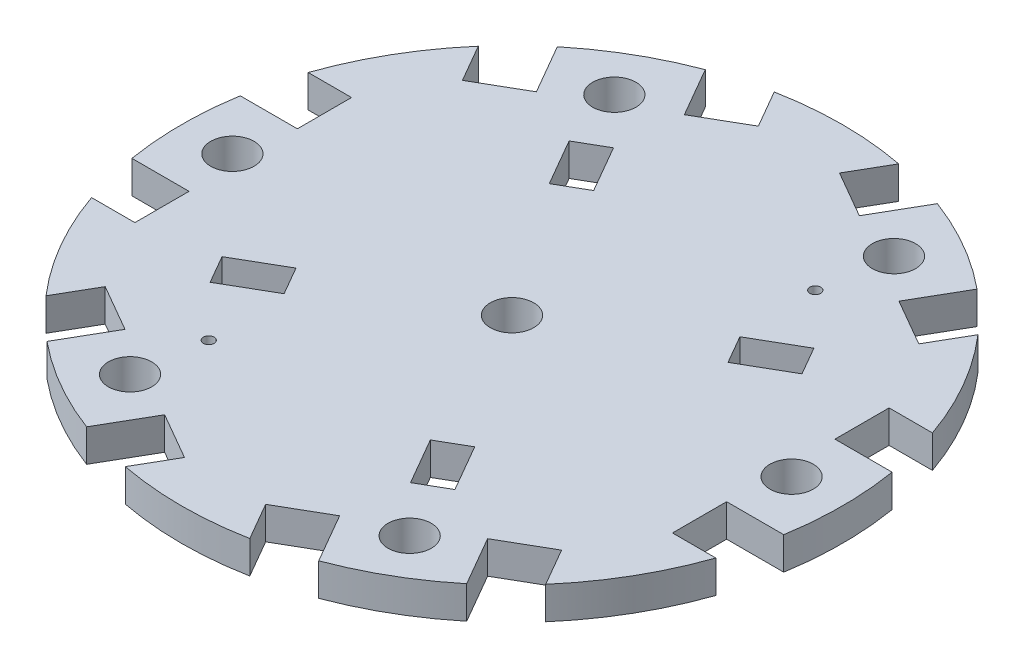
SolidWorks part; units mm, degrees
ref_plane "Alzado" through (0, 0, 0) normal (0, 0, 1) x (1, 0, 0)
ref_plane "Planta" through (0, 0, 0) normal (0, 1, 0) x (1, 0, 0)
ref_plane "Vista lateral" through (0, 0, 0) normal (1, 0, 0) x (0, 0, -1)
sketch "Croquis1" plane through (0, 0, 0) normal (0, 1, 0) x (1, 0, 0)
  circle A0 centre (0, 0) radius 30.5
extrude "Saliente-Extruir1" add sketch "Croquis1" along normal blind 3
sketch "Croquis2" plane through (0, 3, 0) normal (0, 1, 0) x (1, 0, 0)
  circle A0 centre (0, 0) radius 2
extrude "Cortar-Extruir1" cut sketch "Croquis2" against normal blind 4
sketch "Croquis5" plane through (0, 3, 0) normal (0, 1, 0) x (1, 0, 0)
  line L1 (28.8141, -5) -> (30.0874, -5)
  line L2 (28.8141, 5) -> (30.0874, 5)
  line L3 (-24.8141, 10) -> (-28.8141, 10)
  line L4 (24.8141, -5) -> (24.8141, -10)
  line L5 (-24.8141, -10) -> (-28.8141, -10)
  line L6 (24.8141, -5) -> (28.8141, -5)
  line L7 (24.8141, 5) -> (24.8141, 10)
  line L8 (-24.8141, 5) -> (-28.8141, 5)
  line L9 (-24.8141, 5) -> (-24.8141, 10)
  line L10 (-24.8141, -5) -> (-28.8141, -5)
  line L11 (-24.8141, -5) -> (-24.8141, -10)
  line L12 (24.8141, 5) -> (28.8141, 5)
  line L13 (24.8141, -10) -> (28.8141, -10)
  line L14 (24.8141, 10) -> (28.8141, 10)
  line L15 (-28.8141, 5) -> (-30.0874, 5)
  line L16 (-28.8141, -5) -> (-30.0874, -5)
  line L17 (18.7372, 22.4537) -> (19.3738, 23.5564)
  line L18 (-24.8141, 0) -> (-12.407, -21.4896)
  line L19 (-12.407, -21.4896) -> (12.407, -21.4896)
  line L20 (12.407, -21.4896) -> (24.8141, 0)
  line L21 (24.8141, 0) -> (12.407, 21.4896)
  line L22 (12.407, 21.4896) -> (-12.407, 21.4896)
  line L23 (-12.407, 21.4896) -> (-24.8141, 0)
  line L24 (-21.0673, -16.4896) -> (-23.0673, -19.9537)
  line L25 (-3.7468, -26.4896) -> (-5.7468, -29.9537)
  line L26 (-16.7372, -18.9896) -> (-18.7372, -22.4537)
  line L27 (-16.7372, -18.9896) -> (-21.0673, -16.4896)
  line L28 (-8.0769, -23.9896) -> (-10.0769, -27.4537)
  line L29 (-8.0769, -23.9896) -> (-3.7468, -26.4896)
  line L30 (-18.7372, -22.4537) -> (-19.3738, -23.5564)
  line L31 (-10.0769, -27.4537) -> (-10.7136, -28.5564)
  line L32 (10.0769, 27.4537) -> (10.7136, 28.5564)
  line L33 (16.7372, 18.9896) -> (21.0673, 16.4896)
  line L34 (16.7372, 18.9896) -> (18.7372, 22.4537)
  line L35 (8.0769, 23.9896) -> (3.7468, 26.4896)
  line L36 (8.0769, 23.9896) -> (10.0769, 27.4537)
  line L37 (21.0673, 16.4896) -> (23.0673, 19.9537)
  line L38 (3.7468, 26.4896) -> (5.7468, 29.9537)
  line L39 (-3.7468, 26.4896) -> (-5.7468, 29.9537)
  line L40 (-21.0673, 16.4896) -> (-23.0673, 19.9537)
  line L41 (-8.0769, 23.9896) -> (-10.0769, 27.4537)
  line L42 (-8.0769, 23.9896) -> (-3.7468, 26.4896)
  line L43 (-16.7372, 18.9896) -> (-18.7372, 22.4537)
  line L44 (-16.7372, 18.9896) -> (-21.0673, 16.4896)
  line L45 (-10.0769, 27.4537) -> (-10.7136, 28.5564)
  line L46 (-18.7372, 22.4537) -> (-19.3738, 23.5564)
  line L47 (10.0769, -27.4537) -> (10.7136, -28.5564)
  line L48 (18.7372, -22.4537) -> (19.3738, -23.5564)
  line L49 (8.0769, -23.9896) -> (3.7468, -26.4896)
  line L50 (8.0769, -23.9896) -> (10.0769, -27.4537)
  line L51 (16.7372, -18.9896) -> (21.0673, -16.4896)
  line L52 (16.7372, -18.9896) -> (18.7372, -22.4537)
  line L53 (3.7468, -26.4896) -> (5.7468, -29.9537)
  line L54 (21.0673, -16.4896) -> (23.0673, -19.9537)
  circle A0 centre (0, 0) radius 21.4896 construction
  circle A1 centre (0, 0) radius 30.5 construction
  arc A2 (-28.8141, 10) -> (-30.0874, 5) centre (0, 0) ccw
  arc A3 (-5.7468, 29.9537) -> (-10.7136, 28.5564) centre (0, 0) ccw
  arc A4 (-30.0874, -5) -> (-28.8141, -10) centre (0, 0) ccw
  arc A5 (30.0874, -5) -> (28.8141, -10) centre (0, 0) cw
  arc A6 (28.8141, 10) -> (30.0874, 5) centre (0, 0) cw
  arc A7 (-23.0673, -19.9537) -> (-19.3738, -23.5564) centre (0, 0) ccw
  arc A8 (-10.7136, -28.5564) -> (-5.7468, -29.9537) centre (0, 0) ccw
  arc A9 (-19.3738, 23.5564) -> (-23.0673, 19.9537) centre (0, 0) ccw
  arc A10 (19.3738, 23.5564) -> (23.0673, 19.9537) centre (0, 0) cw
  arc A11 (5.7468, 29.9537) -> (10.7136, 28.5564) centre (0, 0) cw
  arc A12 (10.7136, -28.5564) -> (5.7468, -29.9537) centre (0, 0) cw
  arc A13 (23.0673, -19.9537) -> (19.3738, -23.5564) centre (0, 0) cw
  circle M2 centre (0, 0) radius 30.5
extrude "Cortar-Extruir3" cut sketch "Croquis5" against normal blind 4 contours L15 L8 L9 L3 M2 | L14 L7 L12 L2 M2 | L4 L13 L1 L6 M2 | L54 L51 L52 L48 M2 | L49 L53 L47 L50 M2 | L28 L31 L25 L29 M2 | L30 L26 L27 L24 M2 | L10 L16 L5 L11 M2 | L43 L46 L40 L44 M2 | L45 L41 L42 L39 M2 | L38 L35 L36 L32 M2 | L33 L37 L17 L34 M2 region at (27.1844, 3, 7.3876) region at (19.99, 3, 19.8486) region at (27.1844, 3, -7.3876) region at (7.1944, 3, 27.2362) region at (19.99, 3, -19.8486) region at (-7.1944, 3, 27.2362) region at (7.1944, 3, -27.2362) region at (-19.99, 3, 19.8486) region at (-7.1944, 3, -27.2362) region at (-27.1844, 3, 7.3876) region at (-19.99, 3, -19.8486) region at (-27.1844, 3, -7.3876)
sketch "Croquis7" plane through (0, 3, 0) normal (0, 1, 0) x (1, 0, 0)
  line L2 (25.8141, 0) -> (12.907, 22.3556)
  line L3 (12.907, 22.3556) -> (-12.907, 22.3556)
  line L4 (-12.907, 22.3556) -> (-25.8141, 0)
  line L5 (-25.8141, 0) -> (-12.907, -22.3556)
  line L6 (-12.907, -22.3556) -> (12.907, -22.3556)
  line L7 (12.907, -22.3556) -> (25.8141, 0)
  circle A0 centre (25.8141, 0) radius 2
  circle A4 centre (-25.8141, 0) radius 2
  circle A5 centre (0, 0) radius 22.3556 construction
  circle A6 centre (12.907, 22.3556) radius 2
  circle A7 centre (-12.907, -22.3556) radius 2
  circle A8 centre (-12.907, 22.3556) radius 2
  circle A9 centre (12.907, -22.3556) radius 2
extrude "Cortar-Extruir4" cut sketch "Croquis7" against normal blind 10 contours A8 L4 L3 | A4 L4 L5 | A4 L5 L4 | A8 L3 L4 | L2 A6 L3 | L3 A6 L2 | L7 A0 L2 | L2 A0 L7 | A7 L5 L6 | A7 L6 L5 | L6 A9 L7 | L7 A9 L6 | A4 region at (24.7114, 3, 0) region at (26.3654, 3, 0) region at (12.3557, 3, -21.4007) region at (13.1827, 3, -22.8331) region at (13.1827, 3, 22.8331) region at (12.3557, 3, 21.4007) region at (-12.3557, 3, -21.4007) region at (-13.1827, 3, -22.8331) region at (-13.1827, 3, 22.8331) region at (-12.3557, 3, 21.4007) region at (-24.7114, 3, 0) region at (-26.3654, 3, 0)
sketch "Croquis8" plane through (0, 3, 0) normal (0, 1, 0) x (1, 0, 0)
  line L0 (0, 0) -> (12, 0)
  line L1 (12, 0) -> (12, 16)
  line L2 (0, 0) -> (-12, 0)
  line L3 (-12, 0) -> (-12, -16)
  circle A0 centre (12, 16) radius 0.5
  circle A1 centre (-12, -16) radius 0.5
extrude "Cortar-Extruir5" cut sketch "Croquis8" against normal blind 3 contours A1 | A0 region at (11.6564, 3, -16.3436) region at (-11.6564, 3, 15.6564)
sketch "Croquis9" plane through (0, 3, 0) normal (0, 1, 0) x (1, 0, 0)
  line L0 (16.5705, 11.299) -> (-18.0705, -8.701)
  line L1 (-8.701, 18.0705) -> (11.299, -16.5705)
  line L2 (-10, 17.3205) -> (-8.701, 18.0705)
  line L3 (8.701, -18.0705) -> (-11.299, 16.5705)
  line L4 (-16.5705, -11.299) -> (18.0705, 8.701)
  line L5 (25.6318, 16.5306) -> (27.1318, 13.9325)
  line L6 (-10, 17.3205) -> (-11.299, 16.5705)
  line L7 (17.3205, 10) -> (16.5705, 11.299)
  line L8 (10, -17.3205) -> (8.701, -18.0705)
  line L9 (10, -17.3205) -> (11.299, -16.5705)
  line L10 (-7.5, 12.9904) -> (-8.799, 12.2404)
  line L11 (-17.3205, -10) -> (-16.5705, -11.299)
  line L12 (-17.3205, -10) -> (-18.0705, -8.701)
  line L13 (-12.9904, -7.5) -> (-13.7404, -6.201)
  line L14 (17.3205, 10) -> (18.0705, 8.701)
  line L15 (-12.9904, -7.5) -> (-12.2404, -8.799)
  line L16 (12.9904, 7.5) -> (13.7404, 6.201)
  line L17 (12.9904, 7.5) -> (12.2404, 8.799)
  line L18 (7.5, -12.9904) -> (8.799, -12.2404)
  line L19 (7.5, -12.9904) -> (6.201, -13.7404)
  line L21 (-7.5, 12.9904) -> (-6.201, 13.7404)
extrude "Cortar-Extruir6" cut sketch "Croquis9" against normal blind 10 contours L15 L13 L0 L12 L11 L4 | L10 L21 L1 L2 L6 L3 | L17 L16 L4 L14 L7 L0 | L18 L19 L3 L8 L9 L1 region at (15.1554, 3, -8.75) region at (-8.75, 3, -15.1554) region at (-15.1554, 3, 8.75) region at (8.75, 3, 15.1554)
